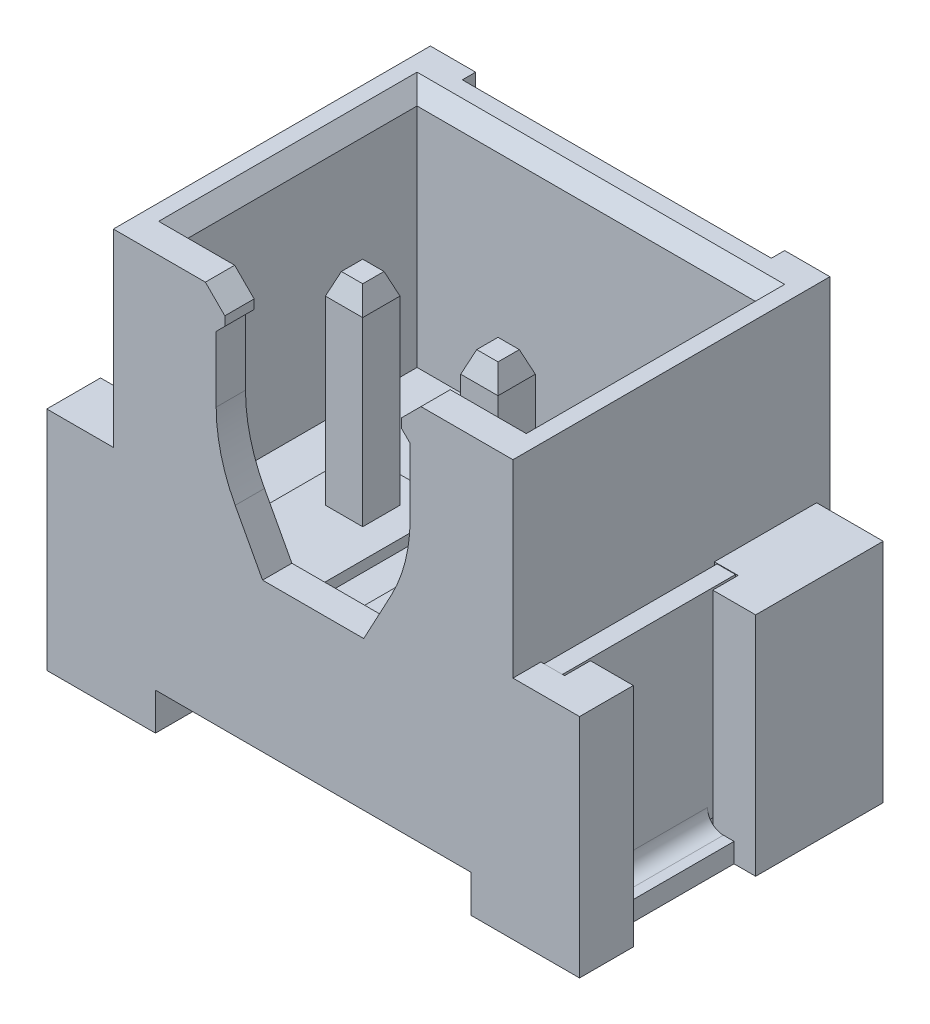
SolidWorks part; units mm, degrees
ref_plane "Front Plane" through (0, 0, 0) normal (0, 0, 1) x (1, 0, 0)
ref_plane "Top Plane" through (0, 0, 0) normal (0, 1, 0) x (1, 0, 0)
ref_plane "Right Plane" through (0, 0, 0) normal (1, 0, 0) x (0, 0, -1)
sketch "Sketch1" plane through (0, 0, 0) normal (0, 1, 0) x (1, 0, 0)
  line L1 (-5, 2.85) -> (5, 2.85)
  line L2 (-5, 2.85) -> (-5, -2.85)
  line L3 (-5, -2.85) -> (5, -2.85)
  line L4 (5, 2.85) -> (5, -2.85)
  line L5 (-5, 2.85) -> (5, -2.85) construction
  line L6 (-5, -2.85) -> (5, 2.85) construction
  point P0 (0, 0)
  dimension "D1" = 10
  dimension "D2" = 5.7
extrude "Boss-Extrude1" add sketch "Sketch1" along normal blind 4.25
sketch "Sketch2" plane through (0, 4.25, 0) normal (0, 1, 0) x (1, 0, 0)
  line L0 (-5, -2.85) -> (5, -2.85) construction
  line L1 (-3.75, 2.85) -> (3.75, 2.85)
  line L2 (-3.75, 2.85) -> (-3.75, -2.85)
  line L3 (-3.75, -2.85) -> (3.75, -2.85)
  line L4 (3.75, 2.85) -> (3.75, -2.85)
  line L5 (-3.75, 2.85) -> (3.75, -2.85) construction
  line L6 (-3.75, -2.85) -> (3.75, 2.85) construction
  line L7 (5, 2.85) -> (-5, 2.85) construction
  point P0 (0, 0)
  point P7 (0, 0)
  point P9 (3.75, 2.85)
  dimension "D1" = 7.5
extrude "Boss-Extrude2" add sketch "Sketch2" along normal blind 3.55
sketch "Sketch3" plane through (0, 0, -2.85) normal (0, 0, -1) x (-1, 0, 0)
  line L0 (-5, 0) -> (5, 0) construction
  line L1 (-3.75, 7.8) -> (-2.9, 7.8)
  line L2 (-3.75, 7.8) -> (-3.75, 0)
  line L3 (-3.75, 0) -> (-2.9, 0)
  line L4 (-2.9, 7.8) -> (-2.9, 0)
  line L5 (0, 0) -> (0, 7.8) construction
  line L6 (-3.75, 7.8) -> (3.75, 7.8) construction
  line L7 (3.75, 0) -> (2.9, 0)
  line L8 (2.9, 7.8) -> (2.9, 0)
  line L9 (3.75, 7.8) -> (2.9, 7.8)
  line L10 (3.75, 7.8) -> (3.75, 0)
  dimension "D1" = 5.8
extrude "Boss-Extrude3" add sketch "Sketch3" along normal blind 0.25
sketch "Sketch4" plane through (0, 7.8, 0) normal (0, 1, 0) x (1, 0, 0)
  line L0 (2.9, 2.85) -> (-2.9, 2.85) construction
  line L1 (-3.2, 2.3) -> (3.2, 2.3)
  line L2 (-3.2, 2.3) -> (-3.2, -2.3)
  line L3 (-3.2, -2.3) -> (3.2, -2.3)
  line L4 (3.2, 2.3) -> (3.2, -2.3)
  line L5 (-3.2, 2.3) -> (3.2, -2.3) construction
  line L6 (-3.2, -2.3) -> (3.2, 2.3) construction
  line L7 (-3.75, -2.85) -> (3.75, -2.85) construction
  line L8 (3.75, -2.85) -> (3.75, 3.1) construction
  point P0 (0, 0)
  point P11 (0, 0)
  dimension "D1" = 0.55
  dimension "D2" = 0.55
  dimension "D3" = 0.55
extrude "Cut-Extrude1" cut sketch "Sketch4" against normal blind 4.55
sketch "Sketch5" plane through (0, 3.25, 0) normal (0, 1, 0) x (1, 0, 0)
  line L0 (-4.271, -2.3848) -> (3.882, -2.3848) construction
  line L1 (-2.175, -2.3) -> (-2.175, 0.2)
  line L2 (-3.2, -2.3) -> (3.2, -2.3) construction
  line L3 (-2.175, 0.2) -> (-0.375, 0.2)
  line L4 (-0.375, 0.2) -> (-0.375, -2.3)
  line L5 (-3.2, -2.3) -> (3.2, -2.3) construction
  line L6 (0, 0) -> (0, 4.0776) construction
  line L7 (-2.175, -2.3) -> (-0.375, -2.3)
  line L8 (2.175, -2.3) -> (0.375, -2.3)
  line L9 (0.375, 0.2) -> (0.375, -2.3)
  line L10 (2.175, 0.2) -> (0.375, 0.2)
  line L11 (2.175, -2.3) -> (2.175, 0.2)
  line L12 (1.62, -1.0001) -> (0.92, -1.0001)
  line L13 (-1.62, -0.3001) -> (-0.92, -0.3001)
  line L14 (-1.62, -0.3001) -> (-1.62, -1.0001)
  line L15 (-1.62, -1.0001) -> (-0.92, -1.0001)
  line L16 (-0.92, -0.3001) -> (-0.92, -1.0001)
  line L17 (-1.62, -0.3001) -> (-0.92, -1.0001) construction
  line L18 (-1.62, -1.0001) -> (-0.92, -0.3001) construction
  line L19 (0.92, -0.3001) -> (0.92, -1.0001)
  line L20 (1.62, -0.3001) -> (0.92, -0.3001)
  line L21 (1.62, -0.3001) -> (1.62, -1.0001)
  point P17 (-1.27, -0.6501)
  dimension "D1" = 0.75
  dimension "D2" = 1.8
  dimension "D3" = 2.5
  dimension "D4" = 0.7
  dimension "D5" = 0.7
  dimension "D6" = 1.27
extrude "Boss-Extrude4" add sketch "Sketch5" along normal blind 0.2
sketch "Sketch6" plane through (0, 3.25, 0) normal (0, 1, 0) x (1, 0, 0)
  line L4 (-0.92, -1.0001) -> (-0.92, -0.3001)
  line L5 (-0.92, -0.3001) -> (-1.62, -0.3001)
  line L6 (-1.62, -0.3001) -> (-1.62, -1.0001)
  line L7 (-1.62, -1.0001) -> (-0.92, -1.0001)
  line L8 (-0.92, -1.0001) -> (-0.92, -0.3001)
  line L9 (-0.92, -0.3001) -> (-1.62, -0.3001)
  line L10 (-1.62, -0.3001) -> (-1.62, -1.0001)
  line L11 (-1.62, -1.0001) -> (-0.92, -1.0001)
  line L12 (1.62, -1.0001) -> (1.62, -0.3001)
  line L13 (1.62, -0.3001) -> (0.92, -0.3001)
  line L14 (0.92, -0.3001) -> (0.92, -1.0001)
  line L15 (0.92, -1.0001) -> (1.62, -1.0001)
  line L16 (1.62, -1.0001) -> (1.62, -0.3001)
  line L17 (1.62, -0.3001) -> (0.92, -0.3001)
  line L18 (0.92, -0.3001) -> (0.92, -1.0001)
  line L19 (0.92, -1.0001) -> (1.62, -1.0001)
  dimension "D1" = 0
  dimension "D2" = 0
extrude "Boss-Extrude5" add sketch "Sketch6" along normal blind 4
chamfer "Chamfer1" distance 0.25 distance2 0.3 3 edges at (3.2, 7.8, 0) (-3.2, 7.8, 0) (0, 7.8, -2.3) first distance on face at (0, 7.8, 0)
sketch "Sketch7" plane through (0, 0, 2.85) normal (0, 0, 1) x (1, 0, 0)
  line L0 (-5.5056, -0.606) -> (2.2675, -0.606) construction
  line L1 (0, 0) -> (0, 7.8) construction
  line L2 (-3.75, 7.8) -> (3.75, 7.8) construction
  line L3 (-2.0231, 7.8) -> (-1.6582, 7.4351)
  line L4 (-1.6582, 7.4351) -> (-1.6582, 7.2631)
  line L5 (-1.6582, 7.2631) -> (-1.8202, 7.1011)
  line L6 (-1.8202, 7.1011) -> (-1.8202, 5.8696)
  line L7 (-1.4637, 4.4511) -> (-0.9493, 3.4925)
  line L8 (-0.9493, 3.4925) -> (0.9493, 3.4925)
  line L9 (1.8202, 7.1011) -> (1.8202, 5.8696)
  line L10 (1.4637, 4.4511) -> (0.9493, 3.4925)
  line L11 (1.6582, 7.2631) -> (1.8202, 7.1011)
  line L12 (1.6582, 7.4351) -> (1.6582, 7.2631)
  line L13 (2.0231, 7.8) -> (1.6582, 7.4351)
  line L14 (-2.0231, 7.8) -> (2.0231, 7.8)
  arc A0 (-1.8202, 5.8696) -> (-1.4637, 4.4511) centre (1.1798, 5.8696) ccw
  arc A1 (1.8202, 5.8696) -> (1.4637, 4.4511) centre (-1.1798, 5.8696) cw
  point P18 (0, 3.4925)
  dimension "D1" = 3
extrude "Cut-Extrude5" cut sketch "Sketch7" against normal up to surface (0.55 mm away) up to face at (0, 4.5643, 2.3)
sketch "Sketch8" plane through (0, 0, 2.85) normal (0, 0, 1) x (1, 0, 0)
  line L0 (0, 0) -> (0, 7.8) construction
  line L1 (-2.96, 0) -> (2.96, 0)
  line L2 (-2.96, 0) -> (-2.96, 0.7)
  line L3 (-2.96, 0.7) -> (2.96, 0.7)
  line L4 (2.96, 0) -> (2.96, 0.7)
  line L5 (-2.96, 0) -> (2.96, 0.7) construction
  line L6 (-2.96, 0.7) -> (2.96, 0) construction
  line L7 (-5, 0) -> (5, 0) construction
  point P0 (0, 0.35)
  point P7 (2.9611, 0)
  point P10 (2.9641, 0.7003)
  dimension "D1" = 5.92
  dimension "D2" = 0.7
extrude "Cut-Extrude6" cut sketch "Sketch8" against normal through all
chamfer "Chamfer2" distance 0.4 distance2 0.15 8 edges at (0.92, 7.25, 0.6501) (1.27, 7.25, 0.3001) (1.62, 7.25, 0.6501) (1.27, 7.25, 1.0001) (-1.62, 7.25, 0.6501) (-1.27, 7.25, 0.3001) (-0.92, 7.25, 0.6501) (-1.27, 7.25, 1.0001) first distance on face at (0.92, 5.35, 0.6501) first distance on face at (1.27, 5.35, 0.3001) first distance on face at (1.62, 5.35, 0.6501) first distance on face at (1.27, 5.35, 1.0001) first distance on face at (-1.62, 5.35, 0.6501) first distance on face at (-1.27, 5.35, 0.3001) first distance on face at (-0.92, 5.35, 0.6501) first distance on face at (-1.27, 5.35, 1.0001)
sketch "Sketch10" plane through (0, 0, 1.0001) normal (0, 0, 1) x (1, 0, 0)
  line L0 (2.96, 0.7) -> (-2.96, 0.7) construction
  line L1 (-1.62, 0.7) -> (-0.92, 0.7)
  line L2 (-1.62, 0.7) -> (-1.62, 0)
  line L3 (-1.62, 0) -> (-0.92, 0)
  line L4 (-0.92, 0.7) -> (-0.92, 0)
  line L5 (-1.62, 6.85) -> (-1.62, 3.45) construction
  line L6 (-0.92, 6.85) -> (-0.92, 3.45) construction
  line L7 (-5, 0) -> (-2.96, 0) construction
  line L8 (0, 0) -> (0, 7.8) construction
  line L9 (-3.45, 7.8) -> (3.45, 7.8) construction
  line L10 (1.62, 0) -> (0.92, 0)
  line L11 (0.92, 0.7) -> (0.92, 0)
  line L12 (1.62, 0.7) -> (0.92, 0.7)
  line L13 (1.62, 0.7) -> (1.62, 0)
extrude "Boss-Extrude6" add sketch "Sketch10" against normal blind 6.45
chamfer "Chamfer3" distance 0.15 distance2 0.4 8 edges at (-1.27, 0, -5.4499) (-0.92, 0.35, -5.4499) (-1.27, 0.7, -5.4499) (-1.62, 0.35, -5.4499) (1.27, 0.7, -5.4499) (0.92, 0.35, -5.4499) (1.27, 0, -5.4499) (1.62, 0.35, -5.4499) first distance on face at (-1.27, 0.35, -5.4499) first distance on face at (1.27, 0.35, -5.4499)
sketch "Sketch11" plane through (0, 0, -2.85) normal (0, 0, -1) x (-1, 0, 0)
  line L0 (-1.27, 0.55) -> (-1.27, 7.8) construction
  line L1 (-1.07, 0.55) -> (-1.47, 0.55) construction
  line L2 (-2.9, 7.8) -> (2.9, 7.8) construction
  line L3 (1.27, 0.7) -> (1.27, 7.8) construction
  line L4 (0.92, 0.7) -> (1.62, 0.7) construction
  line L5 (-0.92, 0.7) -> (0.92, 0.7) construction
  line L6 (-1.82, 0.9) -> (-0.72, 0.9)
  line L7 (-1.82, 0.9) -> (-1.82, 0.7)
  line L8 (-1.82, 0.7) -> (-0.72, 0.7)
  line L9 (-0.72, 0.9) -> (-0.72, 0.7)
  line L10 (-1.82, 0.9) -> (-0.72, 0.7) construction
  line L11 (-1.82, 0.7) -> (-0.72, 0.9) construction
  line L13 (1.82, 0.9) -> (0.72, 0.9)
  line L14 (1.82, 0.9) -> (1.82, 0.7)
  line L15 (1.82, 0.7) -> (0.72, 0.7)
  line L16 (0.72, 0.9) -> (0.72, 0.7)
  line L17 (1.82, 0.9) -> (0.72, 0.7) construction
  line L18 (1.82, 0.7) -> (0.72, 0.9) construction
  point P10 (-1.27, 0.8)
  point P17 (1.27, 0.8)
  dimension "D1" = 0.2
  dimension "D2" = 1.1
extrude "Cut-Extrude7" cut sketch "Sketch11" against normal blind 2
fillet "Fillet1" radius 1 2 edges at (-1.27, 0, 1.0001) (1.27, 0, 1.0001)
sketch "Sketch12" plane through (0, 7.8, 0) normal (0, 1, 0) x (1, 0, 0)
  line L0 (-10.077, -1.9662) -> (-4.5433, -1.9662) construction
  line L1 (5, 0.4556) -> (4.1947, 0.4556)
  line L2 (5, -2.85) -> (5, 2.85) construction
  line L3 (4.1947, 0.4556) -> (4.1947, 0.932)
  line L4 (4.1947, 0.932) -> (3.75, 0.932)
  line L5 (3.75, -2.85) -> (3.75, 3.1) construction
  line L6 (3.75, 0.932) -> (3.75, -2.3265)
  line L7 (3.75, -2.85) -> (3.75, 2.85) construction
  line L8 (3.75, -2.3265) -> (4.1947, -2.3265)
  line L9 (4.1947, -2.3265) -> (4.1947, -1.8406)
  line L10 (4.1947, -1.8406) -> (5, -1.8406)
  line L11 (5, -1.8406) -> (5, 0.4556)
  line L12 (0, 0) -> (0, 5.9973) construction
  line L13 (-4.1947, -1.8406) -> (-5, -1.8406)
  line L14 (-4.1947, -2.3265) -> (-4.1947, -1.8406)
  line L15 (-3.75, -2.3265) -> (-4.1947, -2.3265)
  line L16 (-3.75, 0.932) -> (-3.75, -2.3265)
  line L17 (-4.1947, 0.932) -> (-3.75, 0.932)
  line L18 (-4.1947, 0.4556) -> (-4.1947, 0.932)
  line L19 (-5, 0.4556) -> (-4.1947, 0.4556)
  line L20 (-5, -1.8406) -> (-5, 0.4556)
extrude "Cut-Extrude8" cut sketch "Sketch12" against normal through all
sketch "Sketch13" plane through (0, 4.25, 0) normal (0, 1, 0) x (1, 0, 0)
  line L0 (4.1947, 0.932) -> (3.75, 0.932) construction
  line L1 (3.8, 0.932) -> (4.1447, 0.932)
  line L2 (3.8, 0.932) -> (3.8, -2.3265)
  line L3 (3.8, -2.3265) -> (4.1447, -2.3265)
  line L4 (4.1447, 0.932) -> (4.1447, -2.3265)
  line L5 (3.75, -2.3265) -> (4.1947, -2.3265) construction
  line L6 (4.1947, -2.3265) -> (4.1947, -1.8406) construction
  line L7 (3.75, -2.85) -> (3.75, 3.1) construction
  line L8 (0, 0) -> (0, 4.3739) construction
  line L9 (-3.8, -2.3265) -> (-4.1447, -2.3265)
  line L10 (-4.1447, 0.932) -> (-4.1447, -2.3265)
  line L11 (-3.8, 0.932) -> (-4.1447, 0.932)
  line L12 (-3.8, 0.932) -> (-3.8, -2.3265)
  dimension "D1" = 0.05
  dimension "D2" = 0.05
extrude "Boss-Extrude7" add sketch "Sketch13" against normal blind 4.2
sketch "Sketch14" plane through (4.1447, 0, 0) normal (1, 0, 0) x (0, 0, -1)
  line L0 (-2.3265, 0.05) -> (0.932, 0.05) construction
  line L1 (-1.7906, 0.05) -> (0.4056, 0.05)
  line L2 (-1.7906, 0.05) -> (-1.7906, 0.416)
  line L3 (-1.7906, 0.416) -> (0.4056, 0.416)
  line L4 (0.4056, 0.05) -> (0.4056, 0.416)
  line L5 (0.4556, 0) -> (0.4556, 4.25) construction
  line L6 (-1.8406, 0) -> (-1.8406, 4.25) construction
  dimension "D1" = 0.05
  dimension "D2" = 0.05
extrude "Boss-Extrude8" add sketch "Sketch14" along normal blind 0.5
mirror "Mirror3" about plane through (0, 0, 0) normal (1, 0, 0) of "Boss-Extrude8"
sketch "Sketch15" plane through (0, 0, 0) normal (0, -1, 0) x (1, 0, 0)
  line L1 (-3.8, 2.3265) -> (-4.1447, 2.3265)
  line L2 (-3.8, 2.3265) -> (-3.8, 1.7906)
  line L3 (-3.8, 1.7906) -> (-4.1447, 1.7906)
  line L4 (-4.1447, 2.3265) -> (-4.1447, 1.7906)
  line L5 (-3.8, -0.932) -> (-4.1447, -0.932)
  line L6 (-3.8, -0.932) -> (-3.8, -0.4056)
  line L7 (-3.8, -0.4056) -> (-4.1447, -0.4056)
  line L8 (-4.1447, -0.932) -> (-4.1447, -0.4056)
  line L9 (3.8, 2.3265) -> (4.1447, 2.3265)
  line L10 (3.8, 2.3265) -> (3.8, 1.7906)
  line L11 (3.8, 1.7906) -> (4.1447, 1.7906)
  line L12 (4.1447, 2.3265) -> (4.1447, 1.7906)
  line L13 (3.8, -0.932) -> (4.1447, -0.932)
  line L14 (3.8, -0.932) -> (3.8, -0.4056)
  line L15 (3.8, -0.4056) -> (4.1447, -0.4056)
  line L16 (4.1447, -0.932) -> (4.1447, -0.4056)
extrude "Cut-Extrude9" cut sketch "Sketch15" against normal blind 0.5
sketch "Sketch16" plane through (0, 4.25, 0) normal (0, 1, 0) x (1, 0, 0)
  line L1 (-4.1447, 0.932) -> (-3.8, 0.932)
  line L2 (-4.1447, 0.932) -> (-4.1447, -2.3265)
  line L3 (-4.1447, -2.3265) -> (-3.8, -2.3265)
  line L4 (-3.8, 0.932) -> (-3.8, -2.3265)
  line L5 (4.1447, 0.932) -> (3.8, 0.932)
  line L6 (4.1447, 0.932) -> (4.1447, -2.3265)
  line L7 (4.1447, -2.3265) -> (3.8, -2.3265)
  line L8 (3.8, 0.932) -> (3.8, -2.3265)
extrude "Cut-Extrude10" cut sketch "Sketch16" against normal blind 0.01
fillet "Fillet3" radius 0.3 2 edges at (4.1447, 0.416, 0.6925) (-4.1447, 0.416, 0.6925)
fillet "Fillet4" radius 0.6 2 edges at (3.8, 0.05, 0.6925) (-3.8, 0.05, 0.6925)
